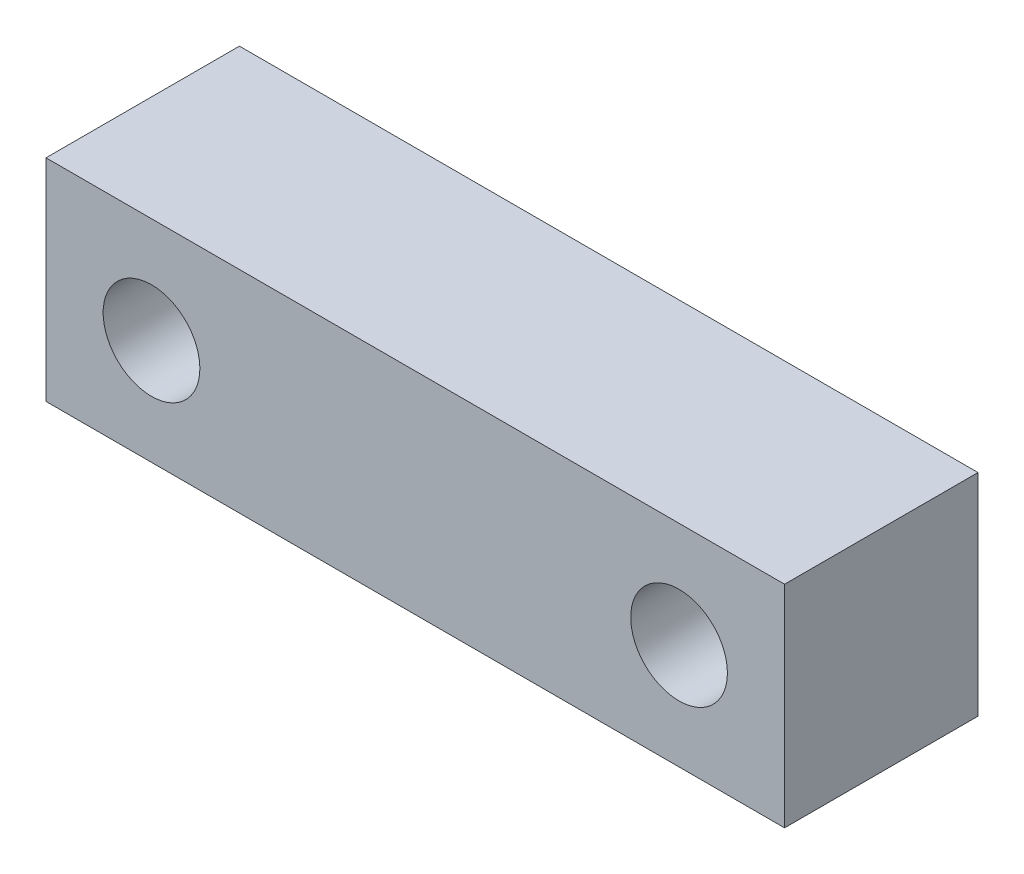
SolidWorks part; units mm, degrees
ref_plane "Front" through (0, 0, 0) normal (0, 0, 1) x (1, 0, 0)
ref_plane "Top" through (0, 0, 0) normal (0, 1, 0) x (1, 0, 0)
ref_plane "Right" through (0, 0, 0) normal (1, 0, 0) x (0, 0, -1)
sketch "草图1" plane through (0, 0, 0) normal (0, 0, 1) x (1, 0, 0)
  line L1 (-21, -6) -> (21, -6)
  line L2 (-21, -6) -> (-21, 6)
  line L3 (-21, 6) -> (21, 6)
  line L4 (21, -6) -> (21, 6)
  line L5 (-21, -6) -> (21, 6) construction
  line L6 (-21, 6) -> (21, -6) construction
  point P0 (0, 0)
  dimension "D1" = 42
  dimension "D2" = 12
extrude "凸台-拉伸1" add sketch "草图1" along normal blind 11
sketch "草图2" plane through (0, 0, 11) normal (0, 0, 1) x (1, 0, 0)
  line L1 (-21, 6) -> (-21, -6) construction
  line L2 (21, -6) -> (21, 6) construction
  line L3 (21, 6) -> (-21, 6) construction
  point P0 (-15, 0)
  point P1 (15, 0)
  dimension "D1" = 6
  dimension "D2" = 6
  dimension "D3" = 6
  dimension "D4" = 6
hole_wizard "Ø5.5 (5.5) 直径孔1" positions "草图3" profile "草图4" hole size "Ø5.5" standard "GB" end condition up to next
sketch "草图3" plane through (0, 0, 11) normal (0, 0, 1) x (1, 0, 0)
  point P0 (-15, 0)
  point P3 (15, 0)
sketch "草图4" plane through (-15, 0, 11) normal (1, 0, 0) x (0, -1, 0)
  line L0 (0, 0) -> (0, 11)
  line L1 (0, 11) -> (2.75, 11)
  line L2 (2.75, 11) -> (2.75, 0)
  line L5 (2.75, 0) -> (0, 0)
  line L11 (0, -6.35) -> (0, 107.95) construction
  dimension "通孔孔直径" = 5.5
  dimension "通孔孔深度" = 11
